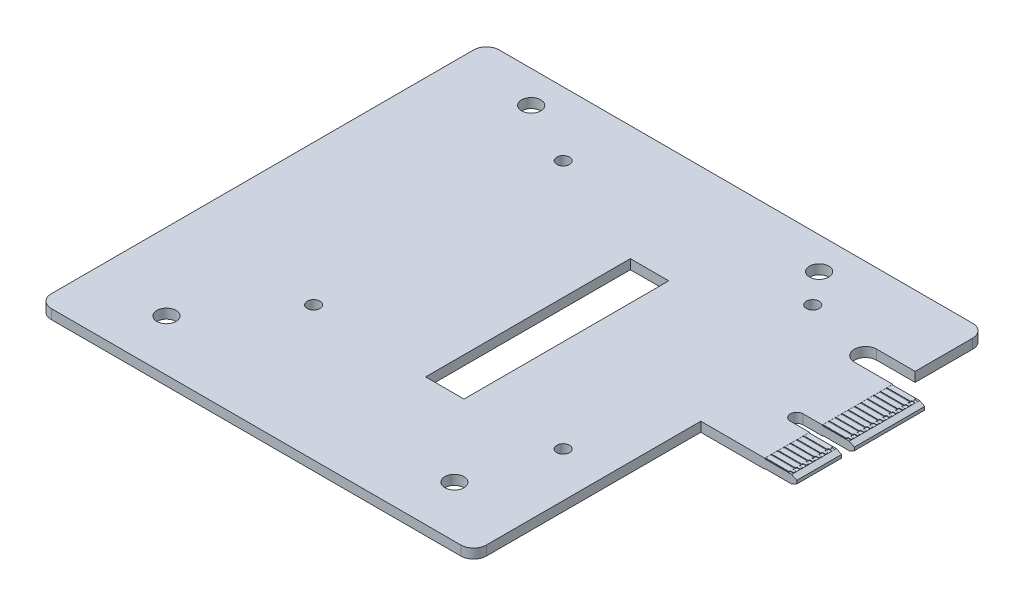
SolidWorks part; units mm, degrees
ref_plane "前视基准面" through (0, 0, 0) normal (0, 0, 1) x (1, 0, 0)
ref_plane "上视基准面" through (0, 0, 0) normal (0, 1, 0) x (1, 0, 0)
ref_plane "右视基准面" through (0, 0, 0) normal (1, 0, 0) x (0, 0, -1)
sketch "草图1" plane through (0, 0, 0) normal (0, 1, 0) x (1, 0, 0)
  line L0 (0, 0) -> (0, 18.5829) construction
  line L1 (39, 35) -> (-39, 35)
  line L2 (39, 35) -> (39, 20.5)
  line L3 (29, -35) -> (-39, -35)
  line L4 (-39, 35) -> (-39, -35)
  line L5 (39, 35) -> (-39, -35) construction
  line L6 (29, -26.0256) -> (-39, 35) construction
  line L9 (39, 0.5) -> (29, 0.5)
  line L10 (29, -35) -> (29, 0.5)
  line L11 (0, 0) -> (-15.2481, 0) construction
  line L13 (39, 0.5) -> (44, 0.5)
  line L15 (39, 20.5) -> (44, 20.5)
  line L16 (44, 0.5) -> (44, 20.5)
  point P0 (0, 0)
  dimension "D1" = 70
  dimension "D2" = 78
  dimension "D3" = 35.5
  dimension "D4" = 68
  dimension "D5" = 5
  dimension "D6" = 20
extrude "凸台-拉伸1" add sketch "草图1" along normal blind 1.5
chamfer "倒角1" distance 0.5 distance2 1 1 edges at (44, 1.5, -10.5) first distance on face at (44, 0.75, -10.5)
chamfer "倒角2" distance 1 distance2 0.5 1 edges at (44, 0, -10.5) first distance on face at (18.25, 0, -5.25)
sketch "草图2" plane through (0, 0, 0) normal (0, 1, 0) x (1, 0, 0)
  line L0 (39, 20.5) -> (33, 20.5)
  line L1 (39, 24) -> (33, 24)
  line L2 (39, 20.5) -> (39, 35) construction
  line L3 (44, 7.5) -> (36, 7.5)
  line L4 (44, 0.5) -> (44, 20.5) construction
  line L5 (44, 9.5) -> (36, 9.5)
  line L6 (29, 0.5) -> (43, 0.5) construction
  line L7 (39, 24) -> (39, 20.5)
  line L8 (44, 9.5) -> (44, 7.5)
  arc A0 (33, 24) -> (33, 20.5) centre (33, 22.25) ccw
  arc A1 (36, 9.5) -> (36, 7.5) centre (36, 8.5) ccw
  dimension "D4" = 8
  dimension "D1" = 3.5
  dimension "D2" = 6
  dimension "D3" = 2
  dimension "D5" = 7
extrude "切除-拉伸1" cut sketch "草图2" along normal through all
fillet "圆角1" radius 2 4 edges at (-39, 0.75, -35) (-39, 0.75, 35) (29, 0.75, 35) (39, 0.75, -35)
sketch "草图3" plane through (0, 0, 0) normal (0, 1, 0) x (1, 0, 0)
  line L0 (37, 35) -> (-37, 35) construction
  line L1 (-39, 33) -> (-39, -33) construction
  circle A0 centre (-27, 30) radius 1.5
  dimension "D1" = 3
  dimension "D2" = 5
  dimension "D3" = 12
extrude "切除-拉伸2" cut sketch "草图3" along normal through all
pattern_linear "阵列(线性)1" count 2 spacing 45 along (1, 0, 0) count 2 spacing 57 along (0, 0, 1) of "切除-拉伸2"
sketch "草图4" plane through (0, 1.5, 0) normal (0, 1, 0) x (1, 0, 0)
  line L0 (-39, 33) -> (-39, -33) construction
  line L1 (-20, 27) -> (-14, 27)
  line L2 (-20, 27) -> (-20, -16)
  line L3 (-20, -16) -> (-14, -16)
  line L4 (-14, 27) -> (-14, -16)
  line L5 (37, 35) -> (-37, 35) construction
  line L7 (19, 27) -> (25, 27)
  line L8 (19, 27) -> (19, -16)
  line L9 (19, -16) -> (25, -16)
  line L10 (25, 27) -> (25, -16)
  dimension "D1" = 19
  dimension "D2" = 6
  dimension "D3" = 8
  dimension "D4" = 43
  dimension "D5" = 33
sketch "草图5" plane through (0, 0, 0) normal (0, 1, 0) x (1, 0, 0)
  line L0 (-17, 27) -> (-17, -18.4701) construction
  line L1 (-20, 27) -> (-14, 27) construction
  line L2 (-20, 5.5) -> (-14, 5.5) construction
  line L3 (-20, 27) -> (-20, -16) construction
  line L4 (-14, 27) -> (-14, -16) construction
  circle A0 centre (-17, 25) radius 1
  dimension "D1" = 2
  dimension "D2" = 39
extrude "切除-拉伸3" cut sketch "草图5" along normal through all
pattern_linear "阵列(线性)2" count 2 spacing 39 along (1, 0, 0) count 2 spacing 39 along (0, 0, 1) of "切除-拉伸3"
sketch "草图9" plane through (0, 0, 0) normal (0, 1, 0) x (1, 0, 0)
  line L0 (-37, -35) -> (27, -35) construction
  line L1 (1.5, 17) -> (7.5, 17)
  line L2 (1.5, 17) -> (1.5, -15)
  line L3 (1.5, -15) -> (7.5, -15)
  line L4 (7.5, 17) -> (7.5, -15)
  line L5 (-39, 33) -> (-39, -33) construction
  dimension "D1" = 20
  dimension "D2" = 32
  dimension "D3" = 6
  dimension "D4" = 40.5
extrude "切除-拉伸6" cut sketch "草图9" along normal through all
sketch "草图6" plane through (0, 1.5, 0) normal (0, 1, 0) x (1, 0, 0)
  line L0 (43, 20.5) -> (33, 20.5) construction
  line L1 (39, 20.5) -> (44, 20.5)
  line L2 (39, 20.5) -> (39, 0.5)
  line L3 (39, 0.5) -> (44, 0.5)
  line L4 (44, 20.5) -> (44, 0.5)
  line L5 (39, 24) -> (39, 33) construction
extrude "切除-拉伸4" cut sketch "草图6" against normal blind 0.1
sketch "草图7" plane through (0, 1.4, 0) normal (0, 1, 0) x (1, 0, 0)
  line L0 (39, 20.5) -> (39, 9.5) construction
  line L1 (39, 20.4) -> (42.7, 20.4)
  line L2 (39, 20.4) -> (39, 19.6)
  line L3 (39, 19.6) -> (42.7, 19.6)
  line L4 (43.2, 20.2) -> (43.2, 19.8)
  line L6 (43.2, 20.5) -> (39, 20.5) construction
  line L7 (43.2, 20.5) -> (43.2, 9.5) construction
  line L10 (43.2, 20.2) -> (42.7, 20.2)
  line L11 (42.7, 20.4) -> (42.7, 20.2)
  line L14 (43.2, 19.8) -> (42.7, 19.8)
  line L15 (42.7, 19.6) -> (42.7, 19.8)
  line L16 (39, 20) -> (40.1334, 20) construction
  dimension "D1" = 0.8
  dimension "D2" = 0.1
  dimension "D3" = 0.4
  dimension "D4" = 0.5
extrude "凸台-拉伸3" add sketch "草图7" along normal blind 0.09
chamfer "倒角3" distance 0.09 distance2 0.3 1 edges at (43.2, 1.49, -20) first distance on face at (43.2, 1.445, -20)
pattern_linear "阵列(线性)3" count 11 spacing 1 along (0, 0, 1) of "凸台-拉伸3", "倒角3"
sketch "草图8" plane through (0, 1.4, 0) normal (0, 1, 0) x (1, 0, 0)
  line L0 (39, 7.5) -> (39, 0.5) construction
  line L1 (39, 7.4) -> (42.7, 7.4)
  line L2 (39, 7.4) -> (39, 6.6)
  line L3 (39, 6.6) -> (42.7, 6.6)
  line L4 (43.2, 7.2) -> (43.2, 6.8)
  line L6 (39, 7.5) -> (43.2, 7.5) construction
  line L7 (42.7, 9.6) -> (42.7, 9.8) construction
  line L10 (43.2, 7.2) -> (42.7, 7.2)
  line L11 (42.7, 7.4) -> (42.7, 7.2)
  line L14 (43.2, 6.8) -> (42.7, 6.8)
  line L15 (42.7, 6.6) -> (42.7, 6.8)
  line L16 (42.7, 9.6) -> (42.7, 9.8) construction
  line L17 (43.2, 7.5) -> (43.2, 0.5) construction
  dimension "D1" = 0.8
  dimension "D2" = 0.1
extrude "凸台-拉伸4" add sketch "草图8" along normal blind 0.09
chamfer "倒角4" distance 0.09 distance2 0.3 1 edges at (43.2, 1.49, -7) first distance on face at (43.2, 1.445, -7)
pattern_linear "阵列(线性)4" count 7 spacing 1 along (0, 0, 1) of "凸台-拉伸4", "倒角4"
ref_plane "基准面1" through (0, 0.75, 0) normal (0, 1, 0) x (1, 0, 0)
mirror "镜向2" about plane through (0, 0.75, 0) normal (0, 1, 0) of "切除-拉伸4"
mirror "镜向5" about plane through (0, 0.75, 0) normal (0, 1, 0) of "凸台-拉伸3"
chamfer "倒角5" distance 0.3 distance2 0.09 1 edges at (43.2, 0.01, -20) first distance on face at (41.9, 0.01, -20)
pattern_linear "阵列(线性)5" count 11 spacing 1 along (0, 0, 1) of "镜向5", "倒角5"
mirror "镜向7" about plane through (0, 0.75, 0) normal (0, 1, 0) of "凸台-拉伸4"
chamfer "倒角6" distance 0.3 distance2 0.09 1 edges at (43.2, 0.01, -7) first distance on face at (41.9, 0.01, -7)
pattern_linear "阵列(线性)6" count 7 spacing 1 along (0, 0, 1) of "镜向7", "倒角6"
